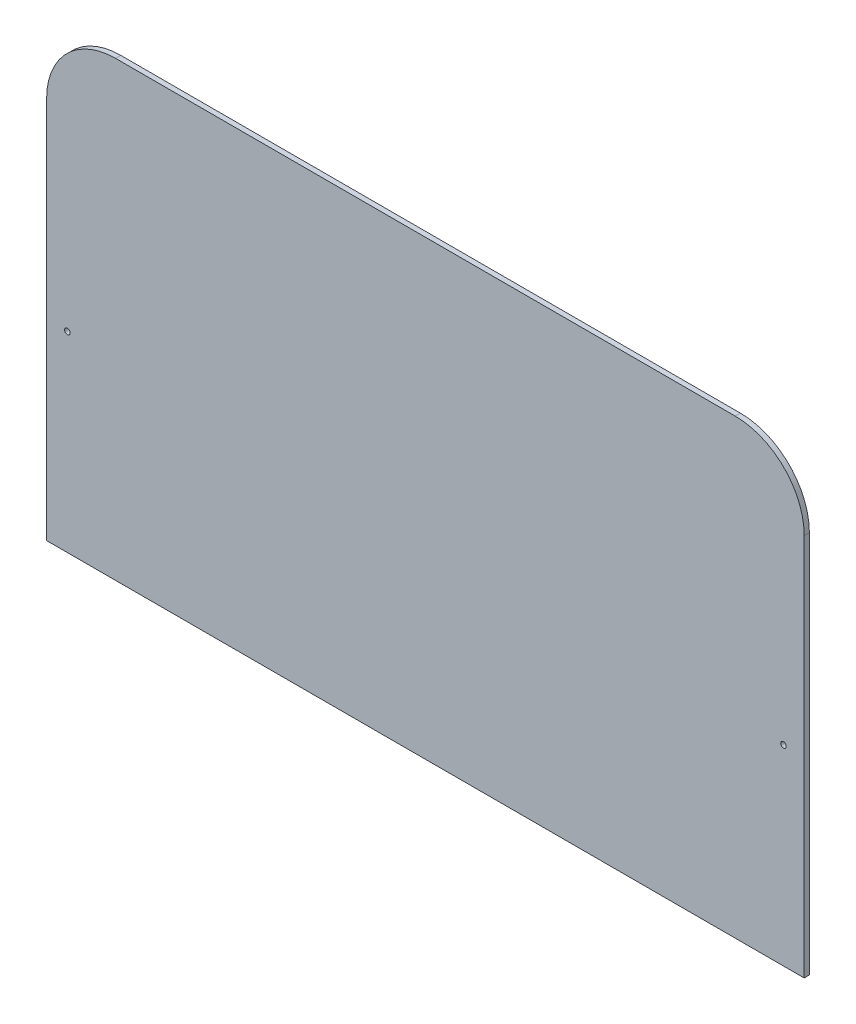
SolidWorks part; units mm, degrees
ref_plane "Plan de face" through (0, 0, 0) normal (0, 0, 1) x (1, 0, 0)
ref_plane "Plan de dessus" through (0, 0, 0) normal (0, 1, 0) x (1, 0, 0)
ref_plane "Plan de droite" through (0, 0, 0) normal (1, 0, 0) x (0, 0, -1)
sketch "Esquisse1" plane through (0, 0, 0) normal (0, 0, 1) x (1, 0, 0)
  line L0 (219.5, -131) -> (216.5, -131) construction
  line L1 (219.5, -131) -> (-219.5, -131)
  line L2 (219.5, -131) -> (219.5, 131)
  line L3 (219.5, 131) -> (-219.5, 131)
  line L4 (-219.5, -131) -> (-219.5, 131)
  line L5 (219.5, -131) -> (-219.5, 131) construction
  line L6 (219.5, 131) -> (-219.5, -131) construction
  point P0 (0, 0)
  dimension "D1" = 439
extrude "Boss.-Extru.1" add sketch "Esquisse1" along normal blind 3
sketch "Esquisse3" plane through (0, 0, 0) normal (0, 0, -1) x (-1, 0, 0)
  line L2 (219.5, -131) -> (-219.5, -131) construction
  line L3 (70.4839, 0) -> (289.8691, 0) construction
  line L4 (219.5, 131) -> (219.5, -131) construction
  line L5 (289.8691, -37.3546) -> (70.4839, -37.3546) construction
  line L6 (219.5, -111.6932) -> (219.5, -104.3068)
  line L7 (219.5, 111.6932) -> (219.5, 104.3068)
  line L10 (-219.5, 131) -> (219.5, 131) construction
  line L11 (163.1932, 131) -> (155.8068, 131)
  line L12 (0, -13.4294) -> (0, 148.2036) construction
  line L14 (110, 75) -> (110, 18.8011) construction
  line L15 (-163.1932, 131) -> (-155.8068, 131)
  line L17 (-219.5, 111.6932) -> (-219.5, 104.3068)
  line L20 (-219.5, -111.6932) -> (-219.5, -104.3068)
  arc A1 (219.5, -111.6932) -> (219.5, -104.3068) centre (217.5, -108) ccw
  arc A3 (219.5, 111.6932) -> (219.5, 104.3068) centre (217.5, 108) cw
  arc A6 (163.1932, 131) -> (155.8068, 131) centre (159.5, 129) ccw
  arc A8 (-163.1932, 131) -> (-155.8068, 131) centre (-159.5, 129) cw
  arc A10 (-219.5, 111.6932) -> (-219.5, 104.3068) centre (-217.5, 108) ccw
  arc A13 (-219.5, -111.6932) -> (-219.5, -104.3068) centre (-217.5, -108) cw
  dimension "D1" = 4.2
  dimension "D2" = 23
  dimension "D3" = 4.2
  dimension "D4" = 60
  dimension "D5" = 2
  dimension "D6" = 2
extrude "Boss.-Extru.3" [suppressed] add sketch "Esquisse3" against normal through all
sketch "Esquisse4" [suppressed] plane through (0, 0, 0) normal (0, 0, -1) x (-1, 0, 0)
  line L1 (225.2325, 0) -> (156.6187, 0) construction
  line L2 (0, 104.1274) -> (0, -30) construction
  circle A0 centre (217.5, -52) radius 1.6
  arc A1 (219.5, -55.6932) -> (219.5, -48.3068) centre (217.5, -52) ccw construction
  circle A5 centre (217.5, 52) radius 1.6
  circle A7 centre (159.5, 73) radius 1.6
  arc A8 (163.1932, 75) -> (155.8068, 75) centre (159.5, 73) ccw construction
  circle A11 centre (60, -73) radius 1.6
  circle A12 centre (159.5, -73) radius 1.6
  circle A13 centre (217.5, -52) radius 1.6
  circle A16 centre (217.5, 52) radius 1.6
  circle A17 centre (217.5, -52) radius 1.6
  circle A20 centre (217.5, 52) radius 1.6
  circle A21 centre (159.5, 73) radius 1.6
  circle A23 centre (60, -73) radius 1.6
  circle A24 centre (159.5, -73) radius 1.6
  circle A25 centre (217.5, -52) radius 1.6
  circle A28 centre (217.5, 52) radius 1.6
  circle A29 centre (217.5, -52) radius 1.6
  circle A32 centre (217.5, 52) radius 1.6
  circle A33 centre (60, -73) radius 1.6
  circle A34 centre (159.5, -73) radius 1.6
  circle A35 centre (217.5, -52) radius 1.6
  circle A38 centre (217.5, 52) radius 1.6
  circle A39 centre (217.5, -52) radius 1.6
  circle A42 centre (217.5, 52) radius 1.6
  circle A43 centre (60, -73) radius 1.6
  circle A44 centre (159.5, -73) radius 1.6
  circle A45 centre (217.5, -52) radius 1.6
  circle A48 centre (217.5, 52) radius 1.6
  circle A50 centre (-217.5, -52) radius 1.6
  circle A51 centre (-217.5, 52) radius 1.6
  circle A53 centre (-159.5, 73) radius 1.6
  dimension "D1" = 3.2
  dimension "D3" = 3.2
extrude "Enlèv. mat.-Extru.1" [suppressed] cut sketch "Esquisse4" against normal through all contours A0 | A5 | A7 | A53 | A51 | A50
fillet "Fillet1" radius 40 2 edges at (219.5, 131, 1.5) (-219.5, 131, 1.5)
sketch "Sketch1" plane through (0, 0, 3) normal (0, 0, 1) x (1, 0, 0)
  circle A0 centre (-207.5, -20) radius 1.6
extrude "Cut-Extrude1" cut sketch "Sketch1" against normal through all
sketch "Sketch2" plane through (0, 0, 3) normal (0, 0, 1) x (1, 0, 0)
  circle A0 centre (207.5, -20) radius 1.6
extrude "Cut-Extrude2" cut sketch "Sketch2" against normal through all
sketch "Sketch3" plane through (0, 0, 3) normal (0, 0, 1) x (1, 0, 0)
  line L0 (-219.5, 91) -> (-219.5, -131) construction
  line L1 (219.5, -131) -> (-219.5, -131)
  line L2 (219.5, -131) -> (219.5, -188)
  line L3 (219.5, -188) -> (-219.5, -188)
  line L4 (-219.5, -131) -> (-219.5, -188)
  dimension "D1" = 57
extrude "Boss-Extrude1" [suppressed] add sketch "Sketch3" against normal blind 3
